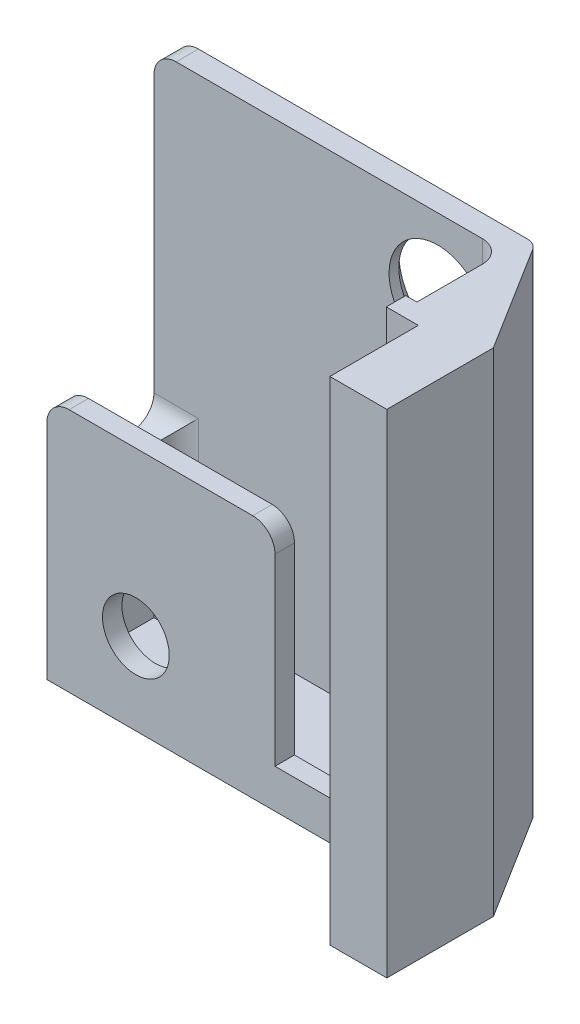
SolidWorks part; units mm, degrees
note: The reader was unsure of these and kept them because the rebuilt part matched: shared geometry of "Sketch3<2>".
ref_plane "Front Plane" through (0, 0, 0) normal (0, 0, 1) x (1, 0, 0)
ref_plane "Top Plane" through (0, 0, 0) normal (0, 1, 0) x (1, 0, 0)
ref_plane "Right Plane" through (0, 0, 0) normal (1, 0, 0) x (0, 0, -1)
sketch "Sketch2" plane through (0, 0, 0) normal (1, 0, 0) x (0, 0, -1)
  line L0 (0, 0) -> (-4.65, 0)
  line L1 (-4.65, 0) -> (-4.65, 17.7)
  line L2 (-4.65, 17.7) -> (-3.85, 17.7)
  line L3 (-3.85, 17.7) -> (-3.85, 0.8)
  line L4 (-3.85, 0.8) -> (-0.7, 0.8)
  line L5 (-0.7, 0.8) -> (-0.7, 17.7)
  line L6 (-0.7, 17.7) -> (0, 17.7)
  line L7 (0, 17.7) -> (0, 0)
  dimension "D2" = 17.7
  dimension "D3" = 3.15
  dimension "D4" = 0.8
  dimension "D5" = 0.7
  dimension "D1" = 0.8
extrude "Boss-Extrude1" add sketch "Sketch2" along normal blind 15.4
sketch "Sketch3" plane through (0, 0, 4.65) normal (0, 0, 1) x (1, 0, 0)
  line L0 (15.4, 0) -> (0, 0) construction
  line L1 (0, 17.7) -> (7.5, 17.7)
  line L2 (0, 17.7) -> (0, 6.2)
  line L3 (0, 6.2) -> (7.5, 6.2)
  line L4 (7.5, 17.7) -> (7.5, 6.2)
  line L7 (15.4, 17.7) -> (15.4, 0) construction
  circle A0 centre (3.2, 2.95) radius 1.2 construction
  circle A1 centre (10.2, 14.95) radius 1.2 construction
  dimension "D3" = 2.4
  dimension "D8" = 2.4
  dimension "D1" = 2.95
  dimension "D4" = 11.5
  dimension "D5" = 7.5
  dimension "D7" = 5.2
  dimension "D6" = 12
  dimension "D2" = 7
extrude "Cut-Extrude2" cut sketch "Sketch3" against normal up to next
sketch "Sketch4" plane through (0, 0, 4.65) normal (0, 0, 1) x (1, 0, 0)
  line L0 (0, 6.2) -> (7.5, 6.2) construction
  line L1 (0, 0) -> (0.8, 0)
  line L2 (0, 0) -> (0, 6.2)
  line L3 (0, 6.2) -> (0.8, 6.2)
  line L4 (0.8, 0) -> (0.8, 6.2)
  line L5 (15.4, 17.7) -> (7.5, 17.7) construction
  line L6 (15.4, 0) -> (12.6, 0)
  line L7 (15.4, 0) -> (15.4, 17.7)
  line L8 (15.4, 17.7) -> (12.6, 17.7)
  line L9 (12.6, 0) -> (12.6, 17.7)
  dimension "D1" = 0.8
  dimension "D2" = 2.8
extrude "Boss-Extrude3" add sketch "Sketch4" against normal through all
sketch "Sketch10" plane through (0, 17.7, 0) normal (0, 1, 0) x (1, 0, 0)
  line L1 (12.6, -0.7) -> (0.8, -0.7) construction
  line L3 (12.2, -0.7) -> (12.2, 0)
  line L4 (15.4, 0) -> (0, 0) construction
  line L5 (12.2, 0) -> (8.2, 0)
  line L6 (8.2, 0) -> (8.2, -0.7)
  line L9 (12.6, -0.7) -> (0, -0.7) construction
  line L10 (8.2, -0.7) -> (12.2, -0.7)
  line L11 (15.4, 0) -> (0, 0) construction
  point P0 (12.6, 0)
  point P1 (10.2, 0)
  dimension "D1" = 4
  dimension "D2" = 2.4
extrude "Cut-Extrude4" cut sketch "Sketch10" against normal blind 16.3
sketch "Sketch6" plane through (0, 0, 3.85) normal (0, 0, -1) x (-1, 0, 0)
  line L0 (-15.4, 0) -> (-15.4, 17.7) construction
  line L1 (-14.6, 17.6) -> (-8.35, 17.6) construction
  line L2 (-14.6, 17.6) -> (-14.6, 13.1) construction
  line L3 (-14.6, 13.1) -> (-10.2, 13.1) construction
  line L4 (-8.35, 17.6) -> (-8.35, 14.95) construction
  line L5 (-0.8, 0.8) -> (-5.05, 0.8)
  line L6 (-0.8, 0.8) -> (-0.8, 4.8)
  line L7 (-0.8, 4.8) -> (-3.2, 4.8)
  line L8 (-5.05, 0.8) -> (-5.05, 2.95)
  arc A0 (-10.2, 13.1) -> (-8.35, 14.95) centre (-10.2, 14.95) ccw construction
  arc A1 (-3.2, 4.8) -> (-5.05, 2.95) centre (-3.2, 2.95) ccw
  dimension "D2" = 1.85
  dimension "D1" = 1.85
  dimension "D3" = 0.8
extrude "Boss-Extrude4" add sketch "Sketch6" along normal blind 0.8
hole_wizard "CSK for M2 Flat Head Machine Screw3" positions "3DSketch3" profile "Sketch8" countersink size "M2" standard "ANSI Metric" end condition through all
sketch3d "3DSketch3"
  point P0 (10.2, 14.95, 4.65)
  point P3 (3.2, 2.95, 4.65)
sketch "Sketch8" plane through (10.2, 14.95, 4.65) normal (1, 0, 0) x (0, -1, 0)
  line L0 (0, 0) -> (0, 4.65)
  line L1 (0, 4.65) -> (1.2, 4.65)
  line L2 (1.2, 4.65) -> (1.2, 1)
  line L3 (1.2, 1) -> (2.2, 0)
  line L5 (2.2, 0) -> (0, 0)
  line L6 (-1.2, 1) -> (-2.2, 0) construction
  line L11 (0, -6.35) -> (0, 107.95) construction
  dimension "Thru Hole Dia." = 2.4
  dimension "Thru Hole Depth" = 4.65
  dimension "Near C'Sink Dia." = 4.4
  dimension "Near C'Sink Angle" = 90
other "Move Face1" face at (4.1, 17.7, 0.35) parameters "D1"=0.6
sketch "Sketch14" plane through (0, 0, 0) normal (0, 0, -1) x (-1, 0, 0)
  line L0 (0, 0) -> (0, 17.1) construction
  line L1 (0, 17.1) -> (-8.2, 17.1)
  line L2 (0, 17.1) -> (0, 8.8)
  line L3 (0, 8.8) -> (-8.2, 8.8)
  line L4 (-8.2, 17.1) -> (-8.2, 8.8)
  line L5 (-8.2, 17.1) -> (0, 17.1) construction
  dimension "D1" = 8.3
extrude "Cut-Extrude6" cut sketch "Sketch14" against normal up to surface (0.7 mm away) up to face at (3.2, 4.15, 0.7)
extrude "Boss-Extrude6" add sketch "Sketch3<2>" against normal up to surface (0.8 mm away) up to face at (11.6, 14.95, 3.85)
sketch "Sketch3<2>" plane through (0, 0, 4.65) normal (0, 0, 1) x (1, 0, 0) same geometry as "Sketch3"
fillet "Fillet3" radius 0.8 8 edges at (0.8, 5.5, 3.85) (0.8, 4.8, 3.45) (0, 8.8, 0.35) (8.2, 8.8, 0.35) (0, 17.7, 4.25) (0.4, 6.2, 3.85) (0.4, 6.2, 0.7) (12.6, 9.25, 3.85)
chamfer "Chamfer1" distance 2.5 distance2 4 1 edges at (15.4, 8.85, 4.65)
sketch "Sketch12" plane through (0, 17.7, 0) normal (0, 1, 0) x (1, 0, 0)
  line L0 (16.5389, 2.7148) -> (17.5509, -0.4) construction
  line L1 (13.3525, 0) -> (15.4, 0)
  line L2 (13.3525, 0) -> (13.3525, 3.18)
  line L3 (13.3525, 3.18) -> (15.4, 3.18)
  line L4 (15.4, 0) -> (15.4, 3.18)
  line L5 (17.5509, -0.4) -> (16.9803, -0.5854) construction
  line L7 (15.9205, 2.2148) -> (16.0705, 2.2148) construction
  line L8 (16.0705, 2.2148) -> (16.9803, -0.5854) construction
  dimension "D1" = 3.18
  dimension "D2" = 0.15
  dimension "D3" = 0.6
  dimension "D4" = 0.5
  dimension "D5" = 18
  dimension "D6" = 0.4
  dimension "D7" = 0.7525
extrude "Boss-Extrude5" add sketch "Sketch12" against normal blind 17.7
fillet "Fillet5" radius 0.5 1 edges at (12.9, 8.85, 4.65)
sketch "Sketch11" plane through (0, 0, 3.85) normal (0, 0, -1) x (-1, 0, 0)
  circle A0 centre (-10.2, 14.95) radius 1.75
  dimension "D1" = 3.5
extrude "Cut-Extrude5" cut sketch "Sketch11" against normal through all and the other way up to next
delete or keep bodies "Body-Delete/Keep 1" [suppressed] type delete bodies bodies 112
mirror "Mirror1" about plane through (13.3525, 0, -3.18) normal (0, 0, -1) of bodies 114
delete or keep bodies "Body-Delete/Keep 2" type delete bodies bodies 114
equation "\"BoardLength\"= 11'mech 305"
equation "\"BoardHeight\"= 16'is"
equation "\"BoardThickness\"= 3'pain"
equation "\"ScrewHoleDiameter\"= 2.4'and"
equation "\"PrintThickness\"= 0.8'suffering"
equation "\"D2@Sketch2\"=\"BoardHeight\"+\"PrintThickness\"+\"Tolerance\"+0.75"
equation "\"D3@Sketch2\"=\"BoardThickness\"+\"Tolerance\""
equation "\"D4@Sketch2\"=\"PrintThickness\""
equation "\"D1@Boss-Extrude1\"=\"BoardLength\"+\"PrintThickness\"*2+\"Tolerance\"*2+1.5+1"
equation "\"D3@Sketch3\"=\"ScrewHoleDiameter\""
equation "\"D1@Sketch3\"=\"PrintThickness\"+2+\"Tolerance\""
equation "\"D1@Sketch4\"=\"PrintThickness\""
equation "\"D7@Sketch3\"=\"PrintThickness\"+3.25+\"Tolerance\"+1"
equation "\"D8@Sketch3\"=\"ScrewHoleDiameter\""
equation "\"MetalRingOuterDiameter\"= 3.7'drop it"
equation "\"D2@Sketch6\"=\"MetalRingOuterDiameter\"/2"
equation "\"DribblerPlateThickness\"= 3.18"
equation "\"D1@Sketch6\"=\"MetalRingOuterDiameter\"/2"
equation "\"Tolerance\"= 0.15"
equation "\"D2@Sketch4\"=\"PrintThickness\"+1+1"
equation "\"D1@Sketch2\"=\"PrintThickness\""
equation "\"D1@Cut-Extrude4\"=\"BoardHeight\"+\"Tolerance\"*2"
